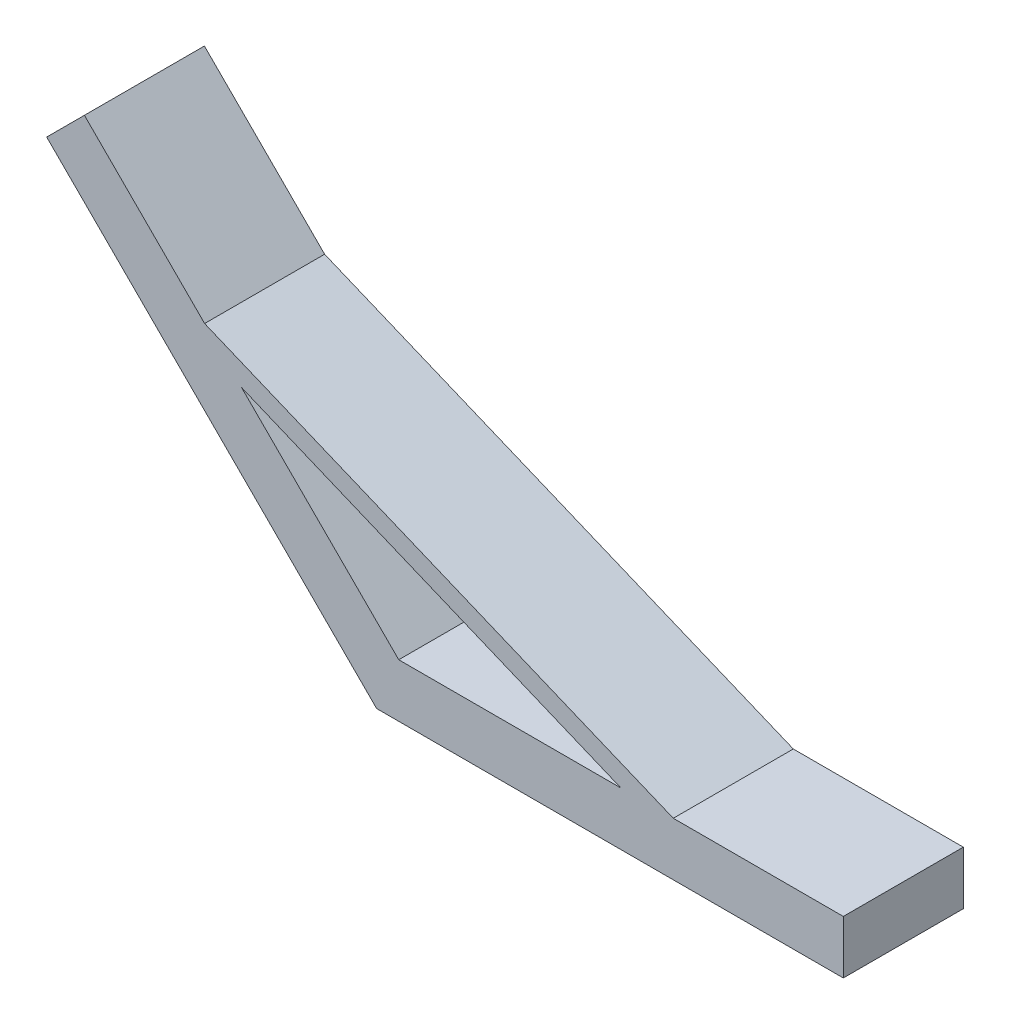
SolidWorks part; units mm, degrees
ref_plane "前视基准面" through (0, 0, 0) normal (0, 0, 1) x (1, 0, 0)
ref_plane "上视基准面" through (0, 0, 0) normal (0, 1, 0) x (1, 0, 0)
ref_plane "右视基准面" through (0, 0, 0) normal (1, 0, 0) x (0, 0, -1)
sketch "草图1" plane through (0, 0, 0) normal (0, 0, 1) x (1, 0, 0)
  line L0 (0, 0) -> (70, 0)
  line L1 (0, 0) -> (-49.4975, 49.4975)
  line L2 (-49.4975, 49.4975) -> (-43.8406, 55.1543)
  line L3 (-43.8406, 55.1543) -> (3.3137, 8)
  line L4 (3.3137, 8) -> (70, 8)
  line L5 (70, 8) -> (70, 0)
  line L6 (-20.2635, 31.5772) -> (36.6569, 8)
  line L7 (36.6569, 8) -> (44.4962, 8)
  line L8 (44.4962, 8) -> (-25.8067, 37.1204)
  line L9 (-25.8067, 37.1204) -> (-20.2635, 31.5772)
  dimension "D1" = 135
  dimension "D2" = 70
  dimension "D3" = 70
  dimension "D4" = 8
  dimension "D5" = 8
  dimension "D6" = 3
extrude "凸台-拉伸1" add sketch "草图1" along normal blind 18 contours L5 L4 L3 L2 L1 L0 | L4 L8 L3 L6 region at (-23.8181, 25.6794, 0) region at (8.7909, 21.223, 0)
